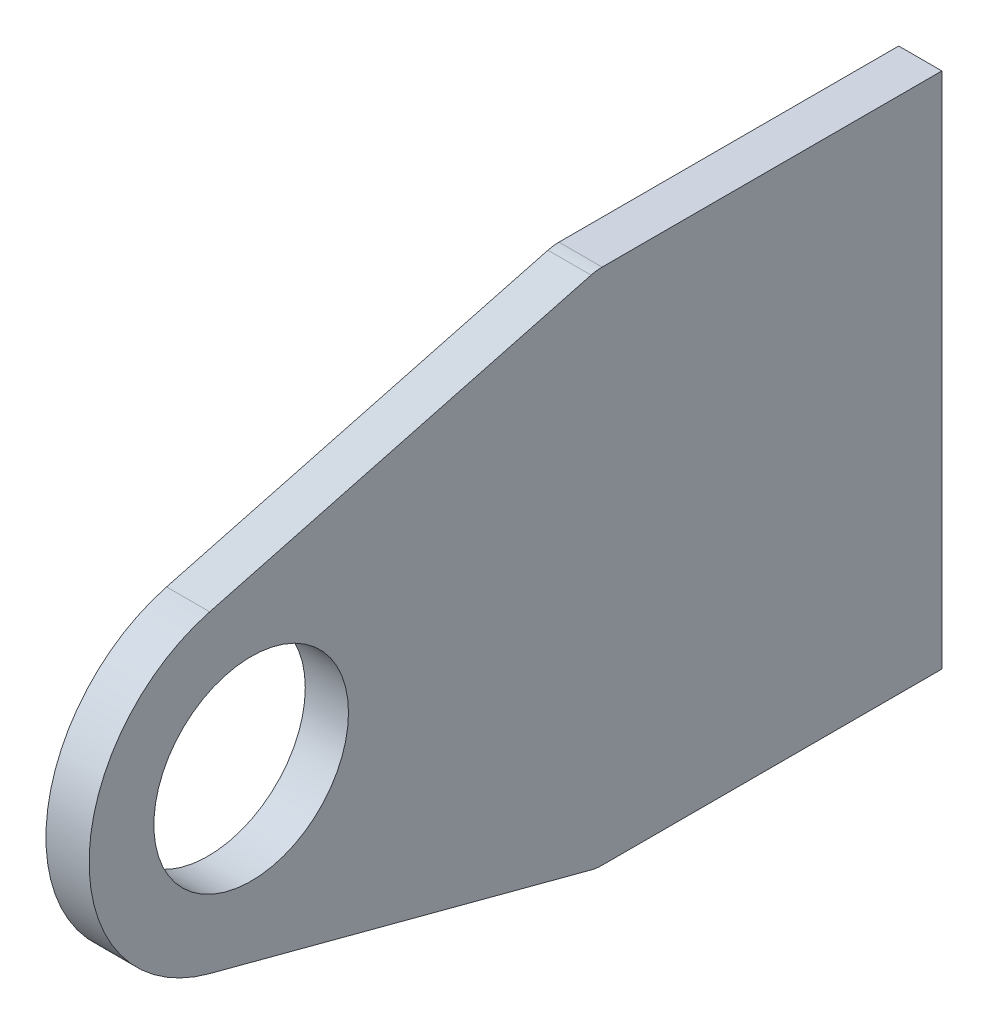
SolidWorks part; units mm, degrees
material "6061-T6 (SS)"
ref_plane "Front" through (0, 0, 0) normal (0, 0, 1) x (1, 0, 0)
ref_plane "Top" through (0, 0, 0) normal (0, 1, 0) x (1, 0, 0)
ref_plane "Right" through (0, 0, 0) normal (1, 0, 0) x (0, 0, -1)
sketch "Sketch1" plane through (0, 0, 0) normal (1, 0, 0) x (0, 0, -1)
  line L0 (0, -38.1) -> (0, 38.1)
  line L1 (0, 38.1) -> (-50.8, 38.1)
  line L2 (0, -38.1) -> (-50.8, -38.1)
  line L3 (-50.8, 38.1) -> (-107.6977, 23.0448)
  line L4 (-107.6977, -23.0448) -> (-50.8, -38.1)
  arc A0 (-107.6977, 23.0448) -> (-107.6977, -23.0448) centre (-101.6, 0) ccw
  circle A1 centre (-101.6, 0) radius 14.3129
  point P4 (0, 0)
  dimension "D3" = 28.6258
  dimension "D4" = 9.525
  dimension "D1" = 50.8
  dimension "D2" = 76.2
  dimension "D5" = 101.6
extrude "Boss-Extrude1" add sketch "Sketch1" along normal blind 6.35
fillet "Fillet1" radius 6.35 2 edges at (3.175, -38.1, 50.8) (3.175, 38.1, 50.8)
